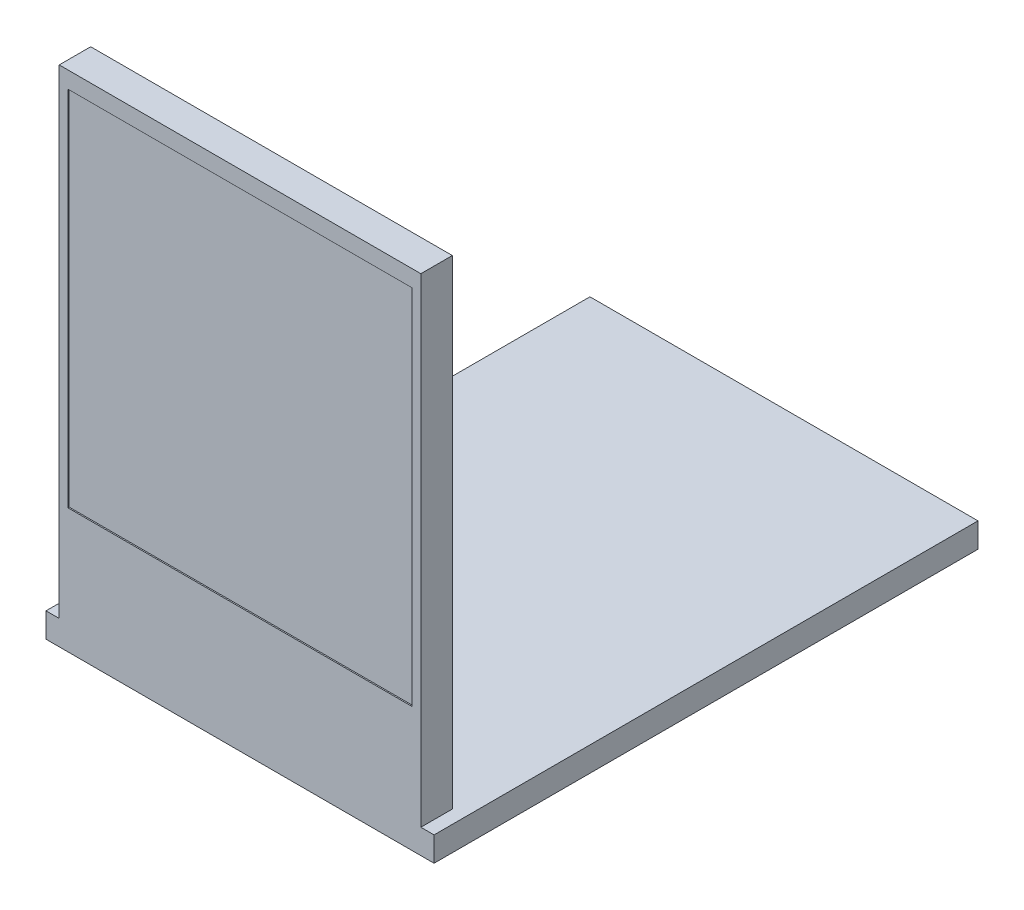
SolidWorks part; units mm, degrees
ref_plane "Front Plane" through (0, 0, 0) normal (0, 0, 1) x (1, 0, 0)
ref_plane "Top Plane" through (0, 0, 0) normal (0, 1, 0) x (1, 0, 0)
ref_plane "Right Plane" through (0, 0, 0) normal (1, 0, 0) x (0, 0, -1)
sketch "Sketch1" plane through (0, 0, 0) normal (0, 1, 0) x (1, 0, 0)
  line L1 (-15.785, 44.25) -> (15.785, 44.25)
  line L2 (-15.785, 44.25) -> (-15.785, 0)
  line L3 (-15.785, 0) -> (15.785, 0)
  line L4 (15.785, 44.25) -> (15.785, 0)
  line L5 (-15.785, 44.25) -> (15.785, 0) construction
  line L6 (-15.785, 0) -> (15.785, 44.25) construction
  point P0 (0, 22.125)
  dimension "D1" = 31.57
  dimension "D2" = 44.25
extrude "Boss-Extrude1" add sketch "Sketch1" against normal blind 2
sketch "Sketch2" plane through (0, 0, 0) normal (0, 0, 1) x (1, 0, 0)
  line L0 (-15.785, -2) -> (15.785, -2) construction
  line L1 (-14.71, 39) -> (14.71, 39)
  line L2 (-14.71, 39) -> (-14.71, 0)
  line L3 (-14.71, 0) -> (14.71, 0)
  line L4 (14.71, 39) -> (14.71, 0)
  line L5 (-14.71, 39) -> (14.71, 0) construction
  line L6 (-14.71, 0) -> (14.71, 39) construction
  line L7 (-15.785, 0) -> (15.785, 0) construction
  point P0 (0, 19.5)
  point P9 (0, 0)
  dimension "D1" = 41
  dimension "D2" = 29.42
extrude "Boss-Extrude2" add sketch "Sketch2" against normal blind 2.56
sketch "Sketch3" plane through (0, 0, 0) normal (0, 0, 1) x (1, 0, 0)
  line L0 (0, 0) -> (0, 39.6936) construction
  line L1 (14.71, 39) -> (-14.71, 39) construction
  line L2 (-14, 37.65) -> (14, 37.65)
  line L3 (-14, 37.65) -> (-14, 8.15)
  line L4 (-14, 8.15) -> (14, 8.15)
  line L5 (14, 37.65) -> (14, 8.15)
  line L6 (-14, 37.65) -> (14, 8.15) construction
  line L7 (-14, 8.15) -> (14, 37.65) construction
  point P3 (0, 22.9)
  dimension "D1" = 28
  dimension "D2" = 1.35
  dimension "D3" = 29.5
extrude "Cut-Extrude1" cut sketch "Sketch3" against normal blind 0.1
